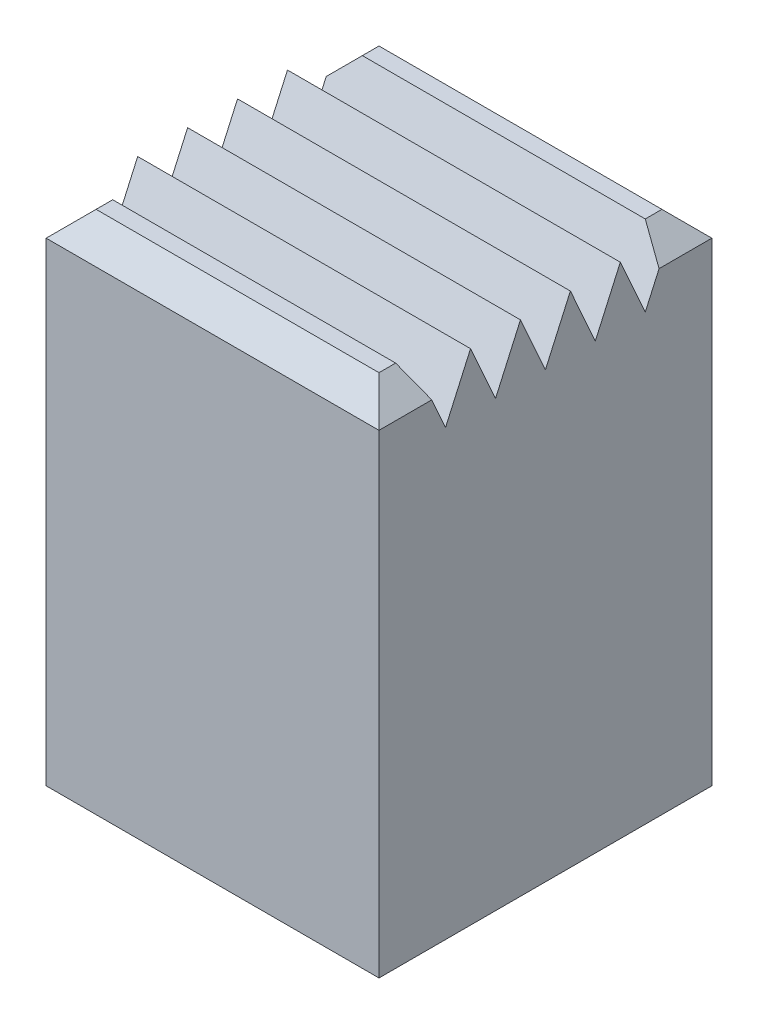
SolidWorks part; units mm, degrees
ref_plane "Front Plane" through (0, 0, 0) normal (0, 0, 1) x (1, 0, 0)
ref_plane "Top Plane" through (0, 0, 0) normal (0, 1, 0) x (1, 0, 0)
ref_plane "Right Plane" through (0, 0, 0) normal (1, 0, 0) x (0, 0, -1)
sketch "Sketch1" plane through (0, 0, 0) normal (0, 1, 0) x (1, 0, 0)
  line L1 (0, 0) -> (4, 0)
  line L2 (0, 0) -> (0, 4)
  line L3 (0, 4) -> (4, 4)
  line L4 (4, 0) -> (4, 4)
  dimension "D1" = 4
extrude "Boss-Extrude1" add sketch "Sketch1" along normal blind 6
sketch "Sketch2" plane through (0, 0, 0) normal (0, -1, 0) x (1, 0, 0)
  line L0 (2, -0.45) -> (2, 0) construction
  line L1 (0.45, -0.45) -> (3.55, -0.45)
  line L2 (0.45, -0.45) -> (0.45, -3.55)
  line L3 (0.45, -3.55) -> (3.55, -3.55)
  line L4 (3.55, -0.45) -> (3.55, -3.55)
  line L5 (0, 0) -> (4, 0) construction
  line L6 (0.45, -2) -> (0, -2) construction
  line L7 (0, -4) -> (0, 0) construction
  dimension "D1" = 3.1
extrude "Cut-Extrude1" cut sketch "Sketch2" against normal blind 4.9
sketch "Sketch3" plane through (0, 0, 0) normal (-1, 0, 0) x (0, 0, 1)
  line L0 (-3.5, 6) -> (-3.2, 5.33)
  line L1 (-4, 6) -> (0, 6) construction
  line L2 (-3.2, 5.33) -> (-2.9, 6)
  line L3 (-3.5, 6) -> (-2.9, 6)
  dimension "D1" = 0.5
  dimension "D2" = 0.6
  dimension "D3" = 0.67
extrude "Cut-Extrude2" cut sketch "Sketch3" against normal up to surface (4 mm away) contours L3 L2 L0 up to face at (4, 3, -2)
pattern_linear "LPattern1" count 5 spacing 0.6 along (0, 0, 1) of "Cut-Extrude2"
chamfer "Chamfer1" distance 0.3 angle 45 6 edges at (4, 6, -0.25) (2, 6, 0) (0, 6, -0.25) (0, 6, -3.75) (2, 6, -4) (4, 6, -3.75)
